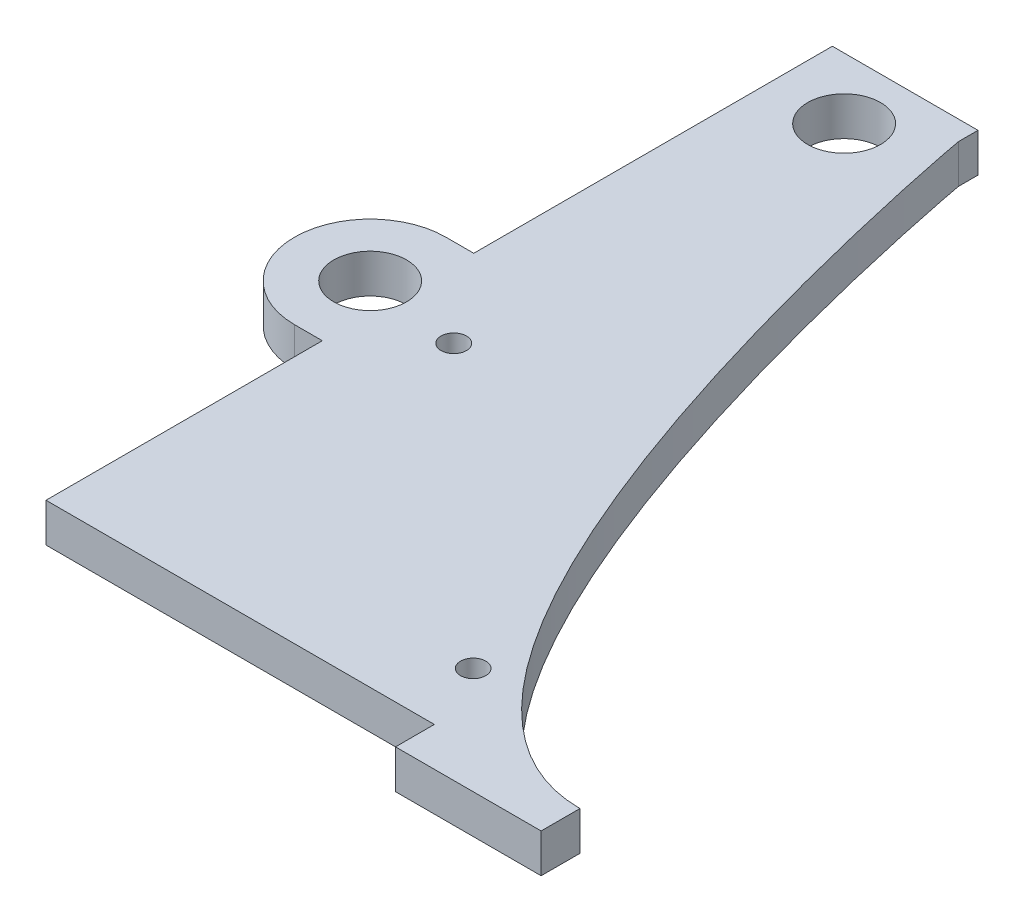
SolidWorks part; units mm, degrees
ref_plane "Front Plane" through (0, 0, 0) normal (0, 0, 1) x (1, 0, 0)
ref_plane "Top Plane" through (0, 0, 0) normal (0, 1, 0) x (1, 0, 0)
ref_plane "Right Plane" through (0, 0, 0) normal (1, 0, 0) x (0, 0, -1)
sketch "Sketch1" plane through (0, 0, 0) normal (0, 1, 0) x (1, 0, 0)
  line L0 (9.525, -53.975) -> (60.325, -53.975) construction
  line L1 (-9.525, -53.975) -> (9.525, -53.975) construction
  line L2 (-9.525, -53.975) -> (-9.525, 53.975) construction
  line L3 (-9.525, 53.975) -> (9.525, 53.975)
  line L4 (9.525, -53.975) -> (9.525, 53.975) construction
  line L5 (-9.525, -53.975) -> (9.525, 53.975) construction
  line L6 (-9.525, 53.975) -> (9.525, -53.975) construction
  line L7 (0, 53.975) -> (0, 45.9867) construction
  line L8 (-9.525, 50.7492) -> (9.525, 50.7492) construction
  line L9 (9.525, 51.435) -> (9.525, 53.975)
  line L10 (60.325, -53.975) -> (60.325, -48.895) construction
  line L11 (60.325, -48.895) -> (-9.525, -48.895) construction
  line L12 (60.325, -53.975) -> (60.325, -48.895) construction
  line L13 (60.325, -48.895) -> (-9.525, -48.895)
  line L14 (-9.525, -48.895) -> (-9.525, 53.975)
  line L15 (31.115, -19.685) -> (31.115, -48.895) construction
  circle A0 centre (0, 45.9867) radius 4.7625
  spline S0 degree 3 poles (9.525, 51.435) (9.525, 51.2145) (27.8191, -48.895) (60.325, -48.895) knots 0 0 0 0 1 1 1 1
  point P4 (0, 0)
  dimension "D5" = 9.525
  dimension "D1" = 107.95
  dimension "D2" = 19.05
  dimension "D3" = 50.8
  dimension "D4" = 2.54
  dimension "D6" = 104.7242
  dimension "D7" = 5.08
  dimension "D8" = 40.64
  dimension "D9" = 29.21
extrude "Boss-Extrude1" add sketch "Sketch1" along normal blind 5.08
sketch "Sketch4" plane through (0, 5.08, 0) normal (0, 1, 0) x (1, 0, 0)
  line L0 (-9.525, 53.975) -> (-9.525, -48.895) construction
  line L1 (60.325, -48.895) -> (41.275, -48.895)
  line L2 (60.325, -48.895) -> (60.325, -53.975)
  line L3 (60.325, -53.975) -> (41.275, -53.975)
  line L4 (41.275, -48.895) -> (41.275, -53.975)
  line L5 (60.325, -48.895) -> (41.275, -53.975) construction
  line L6 (60.325, -53.975) -> (41.275, -48.895) construction
  point P4 (50.8, -51.435)
  dimension "D1" = 50.8
  dimension "D2" = 5.08
extrude "Boss-Extrude2" add sketch "Sketch4" against normal up to surface (5.08 mm away) up to face at (17.145, 0, -2.286)
sketch "Sketch5" plane through (0, 0, 0) normal (0, -1, 0) x (1, 0, 0)
  circle A4 centre (-0.635, 4.445) radius 1.6607
  circle A5 centre (37.465, 40.005) radius 1.651
extrude "Cut-Extrude1" cut sketch "Sketch5" against normal through all both
sketch "Sketch6" plane through (0, 0, 0) normal (0, -1, 0) x (1, 0, 0)
  line L0 (-9.525, 2.8423) -> (-13.1707, 2.8423) construction
  line L1 (-9.525, -53.975) -> (-9.525, 48.895) construction
  line L2 (-13.1707, 12.7483) -> (-9.525, 12.7483)
  line L3 (-13.1707, -7.0637) -> (-9.525, -7.0637)
  line L4 (-9.525, 12.7483) -> (-9.525, 12.053)
  line L5 (-9.525, -7.0637) -> (-9.525, -6.3685)
  line L6 (41.275, 53.975) -> (60.325, 53.975) construction
  circle A0 centre (-13.1707, 2.8423) radius 4.7625
  arc A1 (-9.525, -6.3685) -> (-9.525, 12.053) centre (-13.1707, 2.8423) ccw
  arc A2 (-13.1707, 12.7483) -> (-13.1707, -7.0637) centre (-13.1707, 2.8423) ccw
  dimension "D1" = 9.525
  dimension "D3" = 19.812
  dimension "D2" = 3.6457
  dimension "D4" = 51.1327
extrude "Boss-Extrude3" add sketch "Sketch6" against normal blind 5.08
sketch "Sketch8" plane through (0, 5.08, 0) normal (0, 1, 0) x (1, 0, 0)
  circle A0 centre (-13.1707, -2.8423) radius 4.7625
extrude "Cut-Extrude2" cut sketch "Sketch8" against normal through all
